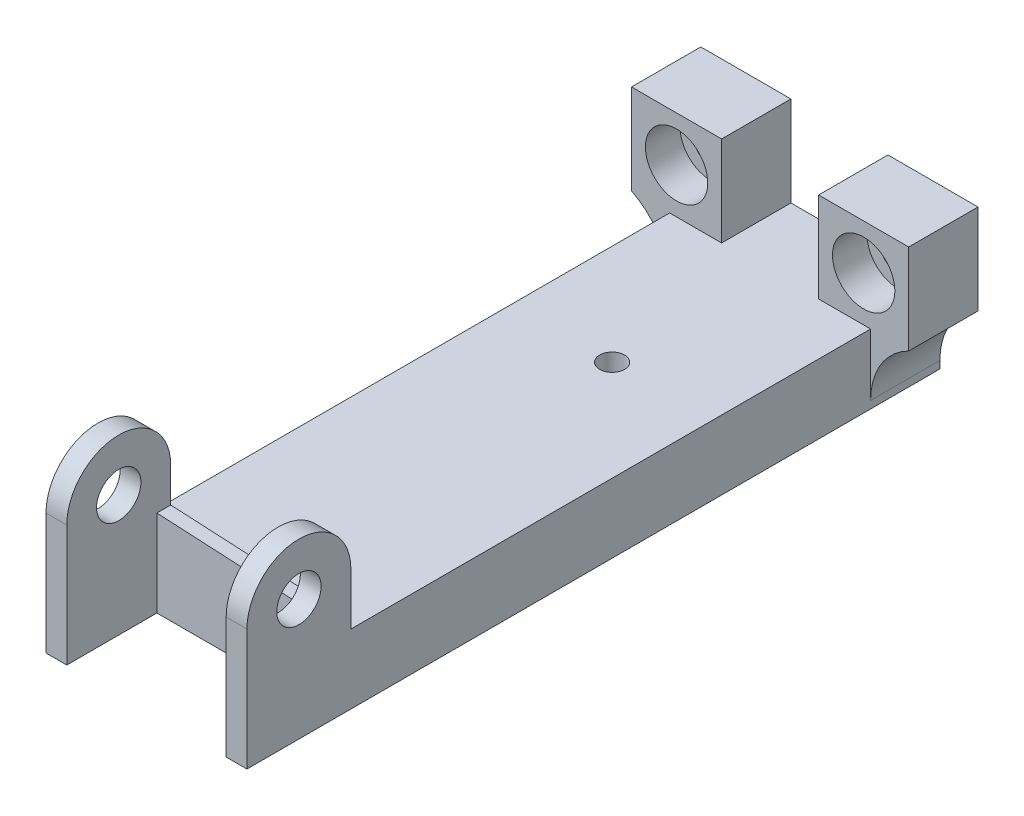
SolidWorks part; units mm, degrees
ref_plane "前视基准面" through (0, 0, 0) normal (0, 0, 1) x (1, 0, 0)
ref_plane "上视基准面" through (0, 0, 0) normal (0, 1, 0) x (1, 0, 0)
ref_plane "右视基准面" through (0, 0, 0) normal (1, 0, 0) x (0, 0, -1)
other "Configuration Table"
sketch "草图1" plane through (0, 0, 0) normal (0, 0, 1) x (1, 0, 0)
  line L1 (-14.2928, 1.196) -> (-1.2928, 1.196)
  line L2 (-14.2928, 1.196) -> (-14.2928, -11.804)
  line L3 (-14.2928, -11.804) -> (-1.2928, -11.804)
  line L4 (-1.2928, 1.196) -> (-1.2928, -11.804)
  line L5 (12.7072, 1.196) -> (25.7072, 1.196)
  line L6 (12.7072, -11.804) -> (25.7072, -11.804)
  line L7 (12.7072, 1.196) -> (12.7072, -11.804)
  line L8 (25.7072, -5.304) -> (25.7072, 1.196)
  line L9 (25.7072, -5.304) -> (25.7072, -11.804)
  circle A0 centre (-7.7928, -5.304) radius 2.65
  circle A1 centre (19.2072, -5.304) radius 2.65
  point P0 (0, 0)
extrude "凸台-拉伸1" add sketch "草图1" along normal blind 10
sketch "草图2" plane through (0, 0, 10) normal (0, 0, 1) x (1, 0, 0)
  circle A0 centre (-7.7928, -5.304) radius 4.5
  circle A1 centre (19.2072, -5.304) radius 4.5
extrude "切除-拉伸2" cut sketch "草图2" against normal blind 5
ref_plane "基准面1" through (5.7072, 0, 0) normal (-1, 0, 0) x (0, 0, 1)
sketch "草图4" plane through (5.7072, 0, 0) normal (-1, 0, 0) x (0, 0, 1)
  line L5 (0, -21.804) -> (0, -11.804)
  line L9 (0, -21.804) -> (85, -21.804)
  line L10 (0, -11.804) -> (85, -11.804)
  line L11 (85, -11.804) -> (85, -21.804)
extrude "凸台-拉伸2" add sketch "草图4" along normal blind 14.5 and the other way blind 14.5
fillet "圆角6" radius 10 2 edges at (20.2072, -11.804, 5) (-8.7928, -11.804, 5)
sketch "草图9" plane through (-8.7928, 0, 0) normal (-1, 0, 0) x (0, 0, 1)
  line L0 (85, -21.804) -> (100, -21.804)
  line L1 (85, -21.804) -> (85, -4.304)
  line L2 (100, -21.804) -> (100, -4.304)
  arc A0 (85, -4.304) -> (100, -4.304) centre (92.5, -4.304) cw
  circle A1 centre (92.5, -4.304) radius 3.2
extrude "凸台-拉伸3" add sketch "草图9" against normal blind 29
sketch "草图10" plane through (0, 0, 100) normal (0, 0, 1) x (1, 0, 0)
  line L0 (17.2072, 3.196) -> (17.2072, -19.804)
  line L2 (-5.7928, -19.804) -> (-5.7928, -21.804)
  line L3 (-5.7928, -19.804) -> (-5.7928, 3.196)
  line L4 (20.2072, 3.196) -> (-8.7928, 3.196) construction
  line L5 (-5.7928, 3.196) -> (17.2072, 3.196)
  line L6 (20.2072, -21.804) -> (-8.7928, -21.804) construction
  line L10 (-5.7928, -21.804) -> (17.2072, -21.804)
  line L11 (17.2072, -21.804) -> (17.2072, -19.804)
extrude "切除-拉伸6" cut sketch "草图10" against normal blind 13
sketch "草图11" plane through (0, 0, 87) normal (0, 0, 1) x (1, 0, 0)
  line L0 (-5.7928, 3.1286) -> (-5.7928, -9.304)
  line L1 (-5.7928, -4.304) -> (-5.7928, -21.804) construction
  line L2 (-5.7928, -9.304) -> (17.2072, -10.5045)
  line L3 (17.2072, -21.804) -> (17.2072, 0.795) construction
  line L5 (17.2072, 3.1286) -> (-5.7928, 3.1286)
  line L6 (-5.7928, -4.304) -> (-5.7928, 3.196) construction
  line L8 (17.2072, 3.1286) -> (17.2072, -10.5045)
extrude "切除-拉伸7" cut sketch "草图11" against normal blind 5
sketch "草图12" plane through (0, -21.804, 0) normal (0, -1, 0) x (1, 0, 0)
  line L4 (5.7072, 5.5) -> (5.7072, -5.5) construction
  circle A0 centre (5.7072, 32.7988) radius 1.8
  circle A1 centre (5.7072, 95.0987) radius 1.8
extrude "切除-拉伸8" cut sketch "草图12" against normal blind 12
